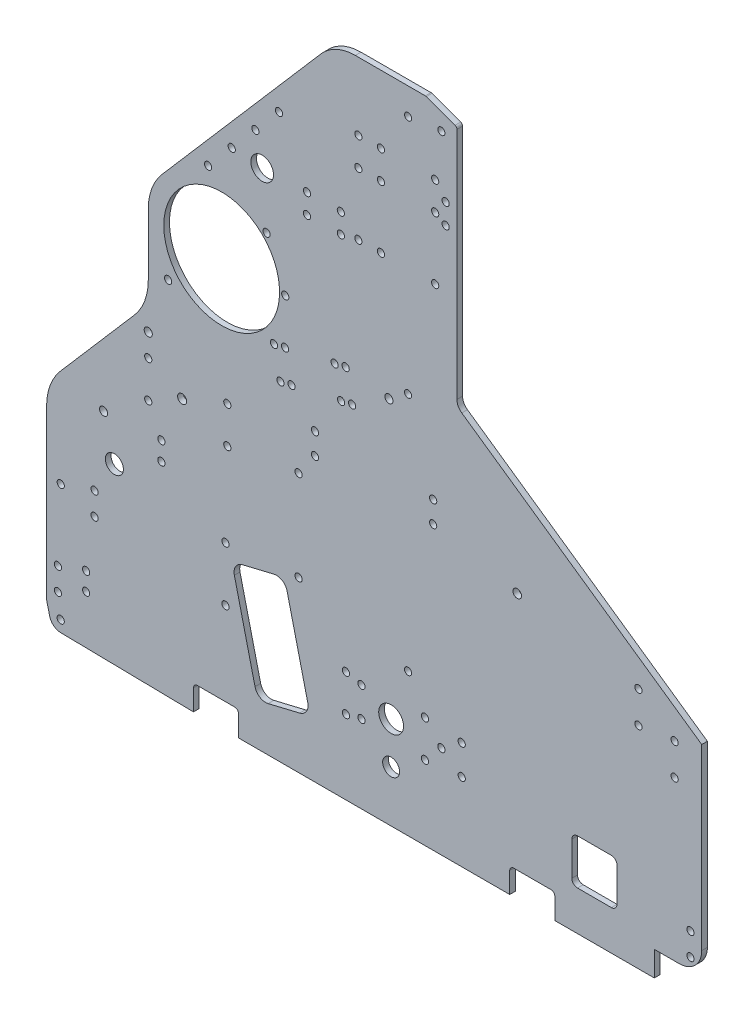
SolidWorks part; units mm, degrees
ref_plane "Front Plane" through (0, 0, 0) normal (0, 0, 1) x (1, 0, 0)
ref_plane "Top Plane" through (0, 0, 0) normal (0, 1, 0) x (1, 0, 0)
ref_plane "Right Plane" through (0, 0, 0) normal (1, 0, 0) x (0, 0, -1)
sketch "Sketch1" plane through (0, 0, 0) normal (0, 0, 1) x (1, 0, 0)
  line L0 (82.55, -20.32) -> (82.55, -6.35)
  line L2 (0, 0) -> (0, 157.48)
  line L4 (368.3, -20.32) -> (368.3, 106.68)
  line L5 (82.55, -6.35) -> (107.95, -6.35)
  line L6 (107.95, -6.35) -> (107.95, -20.32)
  line L7 (107.95, -20.32) -> (260.35, -20.32)
  line L8 (260.35, -20.32) -> (260.35, -6.35)
  line L9 (260.35, -6.35) -> (285.75, -6.35)
  line L10 (285.75, -6.35) -> (285.75, -20.32)
  line L11 (285.75, -20.32) -> (368.3, -20.32)
  line L12 (361.95, 12.7) -> (368.3, 12.7) construction
  line L13 (0, 0) -> (6.35, 0) construction
  line L14 (0.1896, -7.8901) -> (1.7771, -14.2401)
  line L15 (7.8295, -19.0491) -> (82.55, -20.32)
  line L16 (0, 0) -> (0, -6.35)
  line L17 (76.2, 128.905) -> (79.375, 128.905) construction
  line L18 (57.15, 118.5863) -> (101.6, 118.5862) construction
  line L19 (57.15, 118.5863) -> (57.15, 139.2238) construction
  line L20 (101.6, 118.5862) -> (101.6, 139.2237) construction
  line L21 (57.15, 139.2238) -> (101.6, 139.2237) construction
  line L22 (57.15, 118.5863) -> (101.6, 139.2237) construction
  line L23 (101.6, 118.5862) -> (57.15, 139.2238) construction
  line L25 (203.2, 59.805) -> (203.2, 194.805) construction
  line L26 (203.2, 194.805) -> (203.2, 329.805) construction
  line L27 (355.6, 332.105) -> (330.2, 332.105) construction
  line L28 (330.2, 332.105) -> (330.2, 217.805) construction
  line L29 (330.2, 217.805) -> (355.6, 217.805) construction
  line L30 (355.6, 217.805) -> (355.6, 332.105) construction
  line L31 (203.2, 344.805) -> (203.2, 194.805) construction
  line L32 (50.8, 332.105) -> (76.2, 332.105) construction
  line L33 (76.2, 332.105) -> (76.2, 217.805) construction
  line L34 (50.8, 217.805) -> (50.8, 332.105) construction
  line L35 (76.2, 217.805) -> (50.8, 217.805) construction
  line L36 (213.2, 344.805) -> (230.6638, 338.455)
  line L37 (203.2, 344.805) -> (161.925, 344.805)
  line L38 (203.2, 344.805) -> (213.2, 344.805)
  line L39 (348.5362, 344.805) -> (413.4623, 344.805)
  line L40 (348.5362, 344.805) -> (230.6638, 344.805) construction
  line L42 (161.925, 344.805) -> (0, 157.48)
  line L44 (230.6638, 338.455) -> (230.6638, 202.565)
  line L45 (230.6638, 202.565) -> (368.3, 106.68)
  line L46 (213.2, 344.805) -> (-141.0713, 344.805) construction
  circle A0 centre (6.35, 0) radius 2.032
  circle A1 centre (6.35, 12.7) radius 2.032
  circle A2 centre (361.95, 0) radius 2.032
  circle A3 centre (361.95, 12.7) radius 2.032
  arc A5 (1.7771, -14.2401) -> (7.8295, -19.0491) centre (7.9375, -12.7) ccw
  circle A6 centre (7.9375, -12.7) radius 2.032
  arc A7 (0, -6.35) -> (0.1896, -7.8901) centre (6.35, -6.35) ccw
  circle A8 centre (38.1, 78.105) radius 5.08
  circle A9 centre (76.2, 128.905) radius 2.54
  circle A10 centre (101.6, 118.5862) radius 2.032
  circle A11 centre (101.6, 139.2237) radius 2.032
  circle A12 centre (57.15, 139.2238) radius 2.032
  circle A13 centre (57.15, 118.5863) radius 2.032
  circle A15 centre (203.2, 59.805) radius 2
  circle A16 centre (203.2, 194.805) radius 2
  circle A17 centre (203.2, 329.805) radius 2
  circle A18 centre (63.5, 313.055) radius 2.032
  circle A20 centre (355.6, 332.105) radius 2.032
  circle A21 centre (330.2, 332.105) radius 2.032
  circle A22 centre (355.6, 217.805) radius 2.032
  circle A23 centre (330.2, 217.805) radius 2.032
  circle A24 centre (50.8, 332.105) radius 2.032
  circle A25 centre (76.2, 332.105) radius 2.032
  circle A26 centre (50.8, 217.805) radius 2.032
  circle A27 centre (76.2, 217.805) radius 2.032
  circle A28 centre (221.9319, 332.105) radius 2
  circle A29 centre (224.3138, 298.831) radius 2.032
  circle A30 centre (353.06, 100.7351) radius 2.032
  circle A31 centre (332.74, 115.9751) radius 2.032
  circle A32 centre (332.74, 98.1951) radius 2.032
  circle A33 centre (353.06, 82.9551) radius 2.032
  circle A34 centre (117.3562, 280.4276) radius 2.032
  circle A35 centre (104.0678, 265.0548) radius 2.032
  circle A36 centre (90.7795, 249.682) radius 2.032
  circle A38 centre (130.6445, 295.8004) radius 2.032
  circle A39 centre (68.326, 182.9237) radius 2.032
  circle A40 centre (224.3138, 287.401) radius 2.032
  point P82 (203.2, 344.805)
  point P83 (221.9319, 341.63)
  point P90 (368.3, 62.484)
  dimension "D6" = 4.064
  dimension "D10" = 6.35
  dimension "D11" = 4.064
  dimension "D17" = 38.1
  dimension "D27" = 4
  dimension "D31" = 4.064
  dimension "D32" = 41.275
  dimension "D36" = 4.064
  dimension "D47" = 39.624
  dimension "D48" = 4.064
  dimension "D25" = 5.08
  dimension "D26" = 4.064
  dimension "D52" = 4.064
  dimension "D65" = 4.064
  dimension "D69" = 10.16
  dimension "D2" = 127
  dimension "D3" = 13.97
  dimension "D4" = 25.4
  dimension "D5" = 152.4
  dimension "D7" = 12.7
  dimension "D8" = 6.35
  dimension "D9" = 20.32
  dimension "D12" = 12.7
  dimension "D13" = 1.5875
  dimension "D14" = 82.55
  dimension "D15" = 368.3
  dimension "D16" = 6.35
  dimension "D18" = 98.425
  dimension "D19" = 38.1
  dimension "D20" = 50.8
  dimension "D21" = 3.175
  dimension "D22" = 270
  dimension "D23" = 20.6375
  dimension "D24" = 44.45
  dimension "D28" = 135
  dimension "D29" = 12.7
  dimension "D30" = 15
  dimension "D33" = 63.5
  dimension "D34" = 27.4638
  dimension "D35" = 12.7
  dimension "D37" = 114.3
  dimension "D38" = 25.4
  dimension "D39" = 12.7
  dimension "D40" = 157.48
  dimension "D41" = 142.24
  dimension "D42" = 365.125
  dimension "D43" = 10
  dimension "D44" = 6.35
  dimension "D45" = 31.75
  dimension "D46" = 6.35
  dimension "D49" = 6.35
  dimension "D50" = 203.2
  dimension "D51" = 15.24
  dimension "D53" = 17.78
  dimension "D54" = 17.78
  dimension "D55" = 20.32
  dimension "D56" = 15.24
  dimension "D57" = 92.202
  dimension "D58" = 8.382
  dimension "D59" = 20.32
  dimension "D60" = 20.32
  dimension "D61" = 8.382
  dimension "D62" = 20.32
  dimension "D63" = 8.382
  dimension "D64" = 8.382
  dimension "D66" = 35.052
  dimension "D67" = 68.326
  dimension "D68" = 11.43
extrude "Boss-Extrude1" add sketch "Sketch1" along normal blind 3.175 contours L16 A7 L14 A5 L15 L2 A0 A1 A6 region at (171.4477, 119.565, 0)
fillet "Fillet1" radius 2.286 4 edges at (285.75, -6.35, 1.5875) (107.95, -6.35, 1.5875) (260.35, -6.35, 1.5875) (82.55, -6.35, 1.5875)
fillet "Fillet2" radius 6.35 1 edges at (230.6638, 202.565, 1.5875)
sketch "Sketch2" plane through (0, 0, 0) normal (0, 0, -1) x (-1, 0, 0)
  circle A0 centre (-100.5528, 71.086) radius 2.032 construction
  circle A1 centre (-100.5528, 40.606) radius 2.032 construction
  circle A2 centre (-22.225, 18.2025) radius 2.032 construction
  circle A3 centre (-22.225, 8.0425) radius 2.032 construction
  circle A4 centre (-100.5528, 71.086) radius 2.032
  circle A5 centre (-100.5528, 40.606) radius 2.032
  circle A6 centre (-22.225, 18.2025) radius 2.032
  circle A7 centre (-22.225, 8.0425) radius 2.032
extrude "Cut-Extrude1" cut sketch "Sketch2" against normal through all
fillet "Fillet3" radius 1.5875 2 edges at (230.6638, 338.455, 1.5875) (213.2, 344.805, 1.5875)
sketch "Sketch3" plane through (0, 0, 3.175) normal (0, 0, 1) x (1, 0, 0)
  line L0 (132.9524, 63.2646) -> (132.7215, 64.2281) construction
  line L1 (128.3814, 66.8897) -> (110.6828, 62.6472) construction
  line L2 (114.5132, 58.4237) -> (126.8822, 61.3887) construction
  line L3 (108.0212, 58.3071) -> (108.2522, 57.3436) construction
  line L4 (131.2006, 57.703) -> (140.0164, 20.9265) construction
  line L5 (144.0993, 16.7636) -> (132.9524, 63.2646) construction
  line L6 (108.2522, 57.3436) -> (119.3991, 10.8426) construction
  line L7 (121.1509, 16.4042) -> (112.3351, 53.1807) construction
  line L8 (119.3991, 10.8426) -> (119.6301, 9.8791) construction
  line L9 (144.3303, 15.8001) -> (144.0993, 16.7636) construction
  line L10 (137.8383, 15.6835) -> (125.4694, 12.7185) construction
  line L11 (123.9701, 7.2175) -> (141.6687, 11.4601) construction
  line L12 (132.9524, 63.2646) -> (132.7215, 64.2281)
  line L13 (128.3814, 66.8897) -> (110.6828, 62.6472)
  line L14 (114.5132, 58.4237) -> (126.8822, 61.3887)
  line L15 (108.0212, 58.3071) -> (108.2522, 57.3436)
  line L16 (131.2006, 57.703) -> (140.0164, 20.9265)
  line L17 (144.0993, 16.7636) -> (132.9524, 63.2646)
  line L18 (108.2522, 57.3436) -> (119.3991, 10.8426)
  line L19 (121.1509, 16.4042) -> (112.3351, 53.1807)
  line L20 (119.3991, 10.8426) -> (119.6301, 9.8791)
  line L21 (144.3303, 15.8001) -> (144.0993, 16.7636)
  line L22 (137.8383, 15.6835) -> (125.4694, 12.7185)
  line L23 (123.9701, 7.2175) -> (141.6687, 11.4601)
  line L24 (127.7894, 69.3598) -> (110.0908, 65.1172)
  line L25 (105.5512, 57.715) -> (105.7822, 56.7515)
  line L26 (105.7822, 56.7515) -> (116.9291, 10.2505)
  line L27 (116.9291, 10.2505) -> (117.16, 9.287)
  line L28 (124.5622, 4.7475) -> (142.2608, 8.99)
  line L29 (146.8003, 16.3922) -> (146.5694, 17.3557)
  line L30 (146.5694, 17.3557) -> (135.4225, 63.8567)
  line L31 (135.4225, 63.8567) -> (135.1915, 64.8202)
  line L32 (14.605, -0.1369) -> (103.7278, 32.3011) construction
  line L33 (14.605, -0.1369) -> (103.7278, 32.3011)
  line L34 (0, -6.35) -> (0, 157.48) construction
  line L35 (-39.6666, 74.7152) -> (103.7278, 126.9065) construction
  line L36 (26.9875, 46.9531) -> (26.9875, 59.6531) construction
  line L37 (107.95, -20.32) -> (260.35, -20.32) construction
  line L38 (64.5259, 92.5258) -> (64.5259, 102.9405) construction
  arc A0 (132.7215, 64.2281) -> (128.6308, 66.9403) centre (129.2206, 63.3889) ccw construction
  arc A1 (110.6828, 62.6472) -> (110.4377, 62.5791) centre (111.522, 59.1463) ccw construction
  arc A2 (128.6308, 66.9403) -> (128.3814, 66.8897) centre (129.2206, 63.3889) ccw construction
  arc A3 (110.4377, 62.5791) -> (108.0212, 58.3071) centre (111.522, 59.1463) ccw construction
  arc A4 (119.6301, 9.8791) -> (123.7207, 7.1669) centre (123.1309, 10.7183) ccw construction
  arc A5 (141.9139, 11.5281) -> (144.3303, 15.8001) centre (140.8295, 14.9609) ccw construction
  arc A6 (141.6687, 11.4601) -> (141.9139, 11.5281) centre (140.8295, 14.9609) ccw construction
  arc A7 (123.7207, 7.1669) -> (123.9701, 7.2175) centre (123.1309, 10.7183) ccw construction
  arc A8 (132.7215, 64.2281) -> (128.6308, 66.9403) centre (129.2206, 63.3889) ccw
  arc A9 (110.6828, 62.6472) -> (110.4377, 62.5791) centre (111.522, 59.1463) ccw
  arc A10 (128.6308, 66.9403) -> (128.3814, 66.8897) centre (129.2206, 63.3889) ccw
  arc A11 (110.4377, 62.5791) -> (108.0212, 58.3071) centre (111.522, 59.1463) ccw
  arc A12 (119.6301, 9.8791) -> (123.7207, 7.1669) centre (123.1309, 10.7183) ccw
  arc A13 (141.9139, 11.5281) -> (144.3303, 15.8001) centre (140.8295, 14.9609) ccw
  arc A14 (141.6687, 11.4601) -> (141.9139, 11.5281) centre (140.8295, 14.9609) ccw
  arc A15 (123.7207, 7.1669) -> (123.9701, 7.2175) centre (123.1309, 10.7183) ccw
  arc A16 (110.0908, 65.1172) -> (109.6726, 65.0012) centre (111.522, 59.1463) ccw
  arc A17 (109.6726, 65.0012) -> (105.5512, 57.715) centre (111.522, 59.1463) ccw
  arc A18 (117.16, 9.287) -> (124.1369, 4.6613) centre (123.1309, 10.7183) ccw
  arc A19 (124.1369, 4.6613) -> (124.5622, 4.7475) centre (123.1309, 10.7183) ccw
  arc A20 (142.2608, 8.99) -> (142.6789, 9.1061) centre (140.8295, 14.9609) ccw
  arc A21 (142.6789, 9.1061) -> (146.8003, 16.3922) centre (140.8295, 14.9609) ccw
  arc A22 (135.1915, 64.8202) -> (128.2147, 69.446) centre (129.2206, 63.3889) ccw
  arc A23 (128.2147, 69.446) -> (127.7894, 69.3598) centre (129.2206, 63.3889) ccw
  circle A26 centre (134.1438, 208.2281) radius 2.032 construction
  circle A33 centre (26.9875, 46.9531) radius 2.032
  circle A34 centre (26.9875, 59.6531) radius 2.032
  circle A35 centre (7.9375, 53.3031) radius 2.032
  circle A37 centre (32.0306, 100.8109) radius 31.75 construction
  circle A38 centre (32.0306, 100.8109) radius 2.286
  circle A39 centre (123.682, 233.4851) radius 2.032 construction
  circle A40 centre (64.5259, 102.9405) radius 2.032
  circle A41 centre (64.5259, 92.5258) radius 2.032
  circle A42 centre (134.1438, 208.2281) radius 2.032
  circle A43 centre (123.682, 233.4851) radius 2.032
  ellipse E0 centre (124.5974, 48.8487) end of major axis (128.5376, 61.3578) minor radius 6 (131.2006, 57.703) -> (126.8822, 61.3887) ccw construction
  ellipse E1 centre (122.2349, 48.2824) end of major axis (113.0518, 57.6456) minor radius 6 (114.5132, 58.4237) -> (112.3351, 53.1807) ccw construction
  ellipse E2 centre (127.7541, 25.2585) end of major axis (131.6942, 37.7675) minor radius 6 (121.1509, 16.4042) -> (125.4694, 12.7185) ccw construction
  ellipse E3 centre (130.1166, 25.8248) end of major axis (139.2998, 16.4616) minor radius 6 (137.8383, 15.6835) -> (140.0164, 20.9265) ccw construction
  ellipse E4 centre (124.5974, 48.8487) end of major axis (128.5376, 61.3578) minor radius 6 (131.2006, 57.703) -> (126.8822, 61.3887) ccw
  ellipse E5 centre (122.2349, 48.2824) end of major axis (131.4181, 38.9192) minor radius 6 (114.5132, 58.4237) -> (112.3351, 53.1807) ccw
  ellipse E6 centre (127.7541, 25.2585) end of major axis (123.8139, 12.7495) minor radius 6 (121.1509, 16.4042) -> (125.4694, 12.7185) ccw
  ellipse E7 centre (130.1166, 25.8248) end of major axis (139.2998, 16.4616) minor radius 6 (137.8383, 15.6835) -> (140.0164, 20.9265) ccw
  point P93 (26.9875, 53.3031)
  point P115 (32.0306, 100.8109)
  dimension "D3" = 63.5
  dimension "D4" = 4.572
  dimension "D8" = 4.064
  dimension "D2" = 88.9
  dimension "D5" = 7.9375
  dimension "D6" = 19.05
  dimension "D7" = 73.6231
  dimension "D9" = 12.7
  dimension "D10" = 10.4147
  dimension "D11" = 37.5384
  dimension "D12" = 45.5727
  dimension "D1" = 2.54
extrude "Cut-Extrude2" cut sketch "Sketch3" against normal through all contours A22 A23 L24 A16 A17 L25 L26 L27 A18 A19 L28 A20 A21 L29 L30 L31 A15 A12 L20 L18 L15 A11 A9 L13 A10 A8 L12 L17 L21 A13 A14 L23 | A12 A15 L23 A14 A13 L21 L17 L12 A8 A10 L13 A9 A11 L15 L18 L20 E7 L22 E6 L19 E5 L14 E4 L16 | L22 E7 L16 E4 L14 E5 L19 E6 | A38 | A41 | A40 | A35 | A34 | A33 | A43 | A42 region at (137.844, 39.8506, 3.175) region at (126.1758, 37.0536, 3.175) region at (128.1544, 68.6507, 3.175) region at (32.0306, 100.8109, 3.175) region at (64.5259, 102.9405, 3.175) region at (64.5259, 92.5258, 3.175)
sketch "Sketch4" plane through (0, 0, 3.175) normal (0, 0, 1) x (1, 0, 0)
  line L0 (57.15, 139.2238) -> (101.6, 139.2237) construction
  line L1 (168.275, 21.4312) -> (212.725, 21.4312) construction
  line L2 (168.275, 21.4312) -> (168.275, 42.0687) construction
  line L3 (168.275, 42.0687) -> (212.725, 42.0687) construction
  line L4 (212.725, 21.4312) -> (212.725, 42.0687) construction
  line L5 (168.275, 21.4312) -> (212.725, 42.0687) construction
  line L6 (168.275, 42.0687) -> (212.725, 21.4312) construction
  line L7 (57.15, 118.5863) -> (57.15, 139.2238) construction
  line L8 (107.95, -20.32) -> (260.35, -20.32) construction
  line L9 (193.675, 31.75) -> (177.005, 31.75) construction
  line L10 (190.5, 31.75) -> (193.675, 31.75) construction
  line L11 (6.35, 12.7) -> (361.95, 12.7) construction
  line L12 (107.95, -6.35) -> (107.95, -20.32) construction
  line L13 (193.675, 31.75) -> (220.6625, 31.75) construction
  line L14 (177.005, 23.4569) -> (177.005, 40.0431) construction
  line L15 (213.2, 44.805) -> (193.2, 44.805) construction
  line L16 (213.2, 44.805) -> (213.2, 344.805) construction
  line L17 (213.2, 344.805) -> (193.2, 344.805) construction
  line L18 (193.2, 44.805) -> (193.2, 344.805) construction
  line L19 (213.2, 44.805) -> (193.2, 344.805) construction
  line L20 (213.2, 344.805) -> (193.2, 44.805) construction
  line L21 (226.9319, 332.105) -> (226.9319, 31.75) construction
  line L22 (237.33, 40.0431) -> (233.3612, 40.0431) construction
  line L23 (237.33, 23.4569) -> (233.3612, 23.4569) construction
  circle A0 centre (168.275, 42.0687) radius 2.032
  circle A1 centre (212.725, 42.0687) radius 2.032
  circle A2 centre (212.725, 21.4312) radius 2.032
  circle A3 centre (168.275, 21.4312) radius 2.032
  circle A4 centre (193.675, 31.75) radius 6.985
  circle A7 centre (220.6625, 31.75) radius 14.2875 construction
  circle A8 centre (193.675, 31.75) radius 12.7 construction
  circle A9 centre (177.005, 40.0431) radius 2.032
  circle A10 centre (177.005, 23.4569) radius 2.032
  circle A11 centre (237.33, 40.0431) radius 2.032 construction
  circle A12 centre (237.33, 23.4569) radius 2.032 construction
  circle A13 centre (193.675, 8.4667) radius 4.7625
  circle A14 centre (221.9319, 31.75) radius 2.032
  circle A15 centre (221.9319, 31.75) radius 5 construction
  circle A16 centre (221.9319, 332.105) radius 5 construction
  circle A17 centre (233.3612, 23.4569) radius 2.032
  circle A18 centre (233.3612, 40.0431) radius 2.032
  point P0 (190.5, 31.75)
  point P26 (203.2, 194.805)
  point P38 (177.005, 31.75)
  dimension "D1" = 4.064
  dimension "D4" = 13.97
  dimension "D7" = 9.525
  dimension "D10" = 25.4
  dimension "D11" = 28.575
  dimension "D16" = 10
  dimension "D17" = 4.064
  dimension "D18" = 10
  dimension "D2" = 52.07
  dimension "D3" = 3.175
  dimension "D5" = 82.55
  dimension "D6" = 26.9875
  dimension "D8" = 20
  dimension "D9" = 300
  dimension "D12" = 16.67
  dimension "D13" = 16.5862
  dimension "D14" = 60.325
  dimension "D15" = 23.2833
  dimension "D19" = 3.9688
extrude "Cut-Extrude3" cut sketch "Sketch4" against normal through all
sketch "Sketch5" plane through (0, 0, 0) normal (0, 0, -1) x (-1, 0, 0)
  line L0 (-57.15, 223.5947) -> (-57.15, 165.3337)
  line L1 (-161.925, 344.805) -> (-52.7201, 218.4699) construction
  line L2 (-57.15, 165.3337) -> (0, 99.219)
  line L3 (0, -6.35) -> (0, 157.48) construction
  line L4 (-147.864, -30.311) -> (-147.864, -16.0874)
  line L5 (-50.4199, 215.8089) -> (0, 157.48) construction
  line L6 (-57.15, 223.5947) -> (0, 157.48)
  line L7 (0, 157.48) -> (0, 99.219)
  line L10 (-341.63, -6.35) -> (-341.63, -21.2964)
  line L12 (-371.0782, -6.35) -> (-341.63, -6.35)
  line L13 (-285.75, -20.32) -> (-368.3, -20.32) construction
  line L14 (-371.0782, -6.35) -> (-371.0782, -21.2964)
  line L15 (-371.0782, -21.2964) -> (-341.63, -21.2964)
  circle A0 centre (-98.425, 208.2281) radius 32.5437
  circle A3 centre (-264.5736, 128.3328) radius 2.39
  point P8 (0, 0)
  dimension "D3" = 65.0875
  dimension "D8" = 4.78
  dimension "D1" = 38.1
  dimension "D2" = 57.15
  dimension "D4" = 41.275
  dimension "D5" = 41.275
  dimension "D6" = 13.97
  dimension "D9" = 22.2382
  dimension "D10" = 117.7733
  dimension "D11" = 11.6447
  dimension "D12" = 123.5853
extrude "Cut-Extrude5" cut sketch "Sketch5" against normal through all contours A0 | L7 L6 L0 L2 | A3 | L14 L15 L10 L12
fillet "Fillet4" radius 31.75 3 edges at (0, 99.219, 1.5875) (57.15, 165.3337, 1.5875) (57.15, 223.5947, 1.5875)
sketch "Sketch6" plane through (0, 0, 3.175) normal (0, 0, 1) x (1, 0, 0)
  line L0 (285.75, -20.32) -> (341.63, -20.32) construction
  line L1 (298.45, 27.305) -> (317.5, 27.305)
  line L2 (295.275, 24.13) -> (295.275, 5.08)
  line L3 (298.45, 1.905) -> (317.5, 1.905)
  line L4 (320.675, 24.13) -> (320.675, 5.08)
  line L5 (295.275, 27.305) -> (320.675, 1.905) construction
  line L6 (295.275, 1.905) -> (320.675, 27.305) construction
  line L7 (368.3, -6.35) -> (368.3, 106.68) construction
  arc A0 (295.275, 5.08) -> (298.45, 1.905) centre (298.45, 5.08) ccw
  arc A1 (317.5, 1.905) -> (320.675, 5.08) centre (317.5, 5.08) ccw
  arc A2 (317.5, 27.305) -> (320.675, 24.13) centre (317.5, 24.13) cw
  arc A3 (298.45, 27.305) -> (295.275, 24.13) centre (298.45, 24.13) ccw
  point P0 (307.975, 14.605)
  dimension "D2" = 3.175
  dimension "D1" = 25.4
  dimension "D3" = 22.225
  dimension "D4" = 47.625
extrude "Cut-Extrude6" cut sketch "Sketch6" against normal through all
fillet "Fillet5" radius 25.4 1 edges at (161.925, 344.805, 1.5875)
sketch "Sketch8" plane through (0, 0, 0) normal (0, 0, -1) x (-1, 0, 0)
  line L0 (-230.6638, 337.343) -> (-230.6638, 205.8802) construction
  line L1 (-230.6638, 255.905) -> (-175.26, 255.905) construction
  line L2 (-175.26, 255.905) -> (-175.26, 306.705) construction
  line L3 (-175.26, 306.705) -> (-230.6638, 306.705) construction
  line L4 (-173.5432, 344.805) -> (-212.9203, 344.805) construction
  line L7 (-107.95, -20.32) -> (-260.35, -20.32) construction
  circle A0 centre (-218.44, 290.83) radius 3.9687
  circle A1 centre (-218.44, 290.83) radius 2.032
  circle A2 centre (218.44, 265.7972) radius 3.9687
  circle A3 centre (218.44, 265.7972) radius 2.032
  circle A4 centre (-205.74, 290.83) radius 3.9687
  circle A5 centre (-205.74, 290.83) radius 2.032
  circle A6 centre (-187.96, 290.83) radius 3.9687
  circle A7 centre (-187.96, 290.83) radius 2.032
  circle A8 centre (-187.96, 306.705) radius 2.032
  circle A9 centre (-175.26, 290.83) radius 3.9687
  circle A10 centre (-175.26, 290.83) radius 2.032
  circle A11 centre (-205.74, 306.705) radius 2.032
  circle A13 centre (-205.74, 255.905) radius 2.032
  circle A14 centre (-187.96, 255.905) radius 2.032
  circle A16 centre (-218.44, 306.705) radius 2.032
  circle A17 centre (-175.26, 306.705) radius 2.032
  circle A18 centre (-175.26, 255.905) radius 2.032
  circle A19 centre (-218.44, 255.905) radius 2.032
  circle A20 centre (-218.44, 306.705) radius 3.9687
  circle A21 centre (-205.74, 306.705) radius 3.9687
  circle A22 centre (-175.26, 306.705) radius 3.9687
  circle A23 centre (-218.44, 255.905) radius 3.9687
  circle A24 centre (-205.74, 255.905) radius 3.9687
  circle A25 centre (-187.96, 255.905) radius 3.9687
  circle A26 centre (-175.26, 255.905) radius 3.9687
  circle A27 centre (-187.96, 306.705) radius 3.9687
  dimension "D1" = 7.9375
  dimension "D7" = 4.064
  dimension "D13" = 12.2237
  dimension "D2" = 12.2237
  dimension "D3" = 12.7
  dimension "D4" = 17.78
  dimension "D5" = 12.7
  dimension "D6" = 88.9
  dimension "D8" = 38.1
  dimension "D9" = 17.78
  dimension "D10" = 12.7
  dimension "D11" = 55.4037
  dimension "D12" = 12.7
  dimension "D14" = 311.15
extrude "Cut-Extrude7" cut sketch "Sketch8" against normal through all contours A16 | A17 | A18 | A19 | A8 | A14 | A1 | A7 | A10 region at (218.44, 306.705, 0) region at (175.26, 306.705, 0) region at (175.26, 255.905, 0) region at (218.44, 255.905, 0)
sketch "Sketch10" plane through (0, 0, 3.175) normal (0, 0, 1) x (1, 0, 0)
  circle A4 centre (141.6425, 74.6844) radius 2.032 construction
  circle A5 centre (141.6425, 125.4844) radius 2.032 construction
  circle A6 centre (141.6425, 74.6844) radius 2.032
  circle A7 centre (141.6425, 125.4844) radius 2.032
extrude "Cut-Extrude8" cut sketch "Sketch10" against normal through all
sketch "Sketch11" plane through (0, 0, 3.175) normal (0, 0, 1) x (1, 0, 0)
  ellipse E4 centre (150.8814, 138.43) end of major axis (150.8814, 140.462) minor radius 2.032
  ellipse E5 centre (150.8814, 150.495) end of major axis (150.8814, 152.527) minor radius 2.032
  ellipse E6 centre (217.3024, 150.495) end of major axis (217.3024, 152.527) minor radius 2.032
  ellipse E7 centre (217.3024, 138.43) end of major axis (217.3024, 140.462) minor radius 2.032
extrude "Cut-Extrude9" cut sketch "Sketch11" against normal through all
sketch "Sketch12" plane through (0, 0, 0) normal (0, 0, -1) x (-1, 0, 0)
  line L0 (-173.5432, 344.805) -> (-212.9203, 344.805) construction
  circle A0 centre (-165.4175, 264.635) radius 2.032
  circle A1 centre (-203.2, 329.805) radius 2 construction
  circle A2 centre (-165.4175, 253.5225) radius 2.032
  circle A3 centre (-146.3675, 253.5225) radius 2.032
  circle A4 centre (-146.3675, 264.635) radius 2.032
  dimension "D1" = 80.17
  dimension "D2" = 4.064
  dimension "D3" = 37.7825
  dimension "D4" = 11.1125
  dimension "D5" = 19.05
extrude "Cut-Extrude10" cut sketch "Sketch12" against normal through all
sketch "Sketch14" plane through (0, 0, 0) normal (0, 0, -1) x (-1, 0, 0)
  line L0 (-130.6445, 295.8004) -> (-121.1847, 263.6885) construction
  line L1 (-121.1847, 263.6885) -> (-90.7795, 249.682) construction
  line L2 (-154.3272, 336.0154) -> (-64.88, 232.5373) construction
  line L4 (-118.517, 269.4796) -> (-115.3937, 261.0208) construction
  line L5 (-118.517, 269.4796) -> (-126.9758, 266.3562) construction
  line L6 (-126.9758, 266.3562) -> (-123.8524, 257.8974) construction
  line L7 (-115.3937, 261.0208) -> (-123.8524, 257.8974) construction
  line L8 (-118.517, 269.4796) -> (-123.8524, 257.8974) construction
  line L9 (-126.9758, 266.3562) -> (-115.3937, 261.0208) construction
  circle A0 centre (-121.1847, 263.6885) radius 6.376
  dimension "D1" = 22.225
  dimension "D2" = 9.017
extrude "Cut-Extrude11" cut sketch "Sketch14" against normal through all
sketch "Sketch15" plane through (0, 0, 3.175) normal (0, 0, 1) x (1, 0, 0)
  line L1 (27.1508, 77.7471) -> (81.7263, 77.7471) construction
  line L2 (57.15, 139.2237) -> (57.15, 151.9237) construction
  line L3 (27.1508, 77.7471) -> (52.3291, 153.5255) construction
  line L4 (56.0505, 156.8833) -> (192.439, 187.1199) construction
  circle A0 centre (27.1508, 77.7471) radius 2.159 construction
  circle A1 centre (27.1508, 77.7471) radius 2.159 construction
  circle A2 centre (57.15, 139.2237) radius 2.032 construction
  circle A3 centre (57.15, 139.2237) radius 2.032 construction
  circle A4 centre (57.15, 151.9237) radius 2.286
  circle A5 centre (192.439, 187.1199) radius 2.286
  circle A6 centre (57.15, 151.9237) radius 5.08 construction
  arc A9 (163.8737, 173.6806) -> (164.5125, 170.7993) centre (165.557, 172.5423) ccw construction
  arc A10 (173.4398, 172.7784) -> (172.801, 175.6597) centre (171.7565, 173.9167) ccw construction
  arc A11 (172.801, 175.6597) -> (173.4398, 172.7784) centre (171.7565, 173.9167) ccw construction
  arc A12 (164.5125, 170.7993) -> (163.8737, 173.6806) centre (165.557, 172.5423) ccw construction
  arc A13 (169.1589, 192.0883) -> (169.7976, 189.2071) centre (168.1143, 190.3453) ccw construction
  arc A14 (169.7976, 189.2071) -> (169.1589, 192.0883) centre (168.1143, 190.3453) ccw construction
  arc A15 (160.2316, 190.1092) -> (160.8704, 187.2279) centre (161.9149, 188.9709) ccw construction
  arc A16 (160.8704, 187.2279) -> (160.2316, 190.1092) centre (161.9149, 188.9709) ccw construction
  arc A17 (129.7766, 166.1214) -> (130.4154, 163.2402) centre (131.4599, 164.9832) ccw construction
  arc A18 (139.3426, 165.2193) -> (138.7039, 168.1005) centre (137.6593, 166.3576) ccw construction
  arc A19 (138.7039, 168.1005) -> (139.3426, 165.2193) centre (137.6593, 166.3576) ccw construction
  arc A20 (130.4154, 163.2402) -> (129.7766, 166.1214) centre (131.4599, 164.9832) ccw construction
  arc A21 (135.7005, 181.6479) -> (135.0617, 184.5292) centre (134.0172, 182.7862) ccw construction
  arc A22 (135.0617, 184.5292) -> (135.7005, 181.6479) centre (134.0172, 182.7862) ccw construction
  arc A23 (126.1345, 182.55) -> (126.7732, 179.6688) centre (127.8177, 181.4118) ccw construction
  arc A24 (126.7732, 179.6688) -> (126.1345, 182.55) centre (127.8177, 181.4118) ccw construction
  arc A25 (163.8737, 173.6806) -> (164.5125, 170.7993) centre (165.557, 172.5423) ccw
  arc A26 (173.4398, 172.7784) -> (172.801, 175.6597) centre (171.7565, 173.9167) ccw
  arc A27 (172.801, 175.6597) -> (173.4398, 172.7784) centre (171.7565, 173.9167) ccw
  arc A28 (164.5125, 170.7993) -> (163.8737, 173.6806) centre (165.557, 172.5423) ccw
  arc A29 (169.1589, 192.0883) -> (169.7976, 189.2071) centre (168.1143, 190.3453) ccw
  arc A30 (169.7976, 189.2071) -> (169.1589, 192.0883) centre (168.1143, 190.3453) ccw
  arc A31 (160.2316, 190.1092) -> (160.8704, 187.2279) centre (161.9149, 188.9709) ccw
  arc A32 (160.8704, 187.2279) -> (160.2316, 190.1092) centre (161.9149, 188.9709) ccw
  arc A33 (129.7766, 166.1214) -> (130.4154, 163.2402) centre (131.4599, 164.9832) ccw
  arc A34 (139.3426, 165.2193) -> (138.7039, 168.1005) centre (137.6593, 166.3576) ccw
  arc A35 (138.7039, 168.1005) -> (139.3426, 165.2193) centre (137.6593, 166.3576) ccw
  arc A36 (130.4154, 163.2402) -> (129.7766, 166.1214) centre (131.4599, 164.9832) ccw
  arc A37 (135.7005, 181.6479) -> (135.0617, 184.5292) centre (134.0172, 182.7862) ccw
  arc A38 (135.0617, 184.5292) -> (135.7005, 181.6479) centre (134.0172, 182.7862) ccw
  arc A39 (126.1345, 182.55) -> (126.7732, 179.6688) centre (127.8177, 181.4118) ccw
  arc A40 (126.7732, 179.6688) -> (126.1345, 182.55) centre (127.8177, 181.4118) ccw
  dimension "D2" = 4.572
  dimension "D6" = 10.16
  dimension "D1" = 12.7
  dimension "D3" = 139.7
  dimension "D4" = 12.5
extrude "Cut-Extrude12" cut sketch "Sketch15" against normal through all
sketch "Sketch16" plane through (0, 0, 3.175) normal (0, 0, 1) x (1, 0, 0)
  circle A0 centre (98.425, 208.2281) radius 34.925 construction
  circle A1 centre (98.425, 208.2281) radius 34.925
  circle A2 centre (98.425, 208.2281) radius 36.195
  dimension "D1" = 1.27
fillet "Fillet6" radius 12.7 1 edges at (368.3, -6.35, 1.5875)
